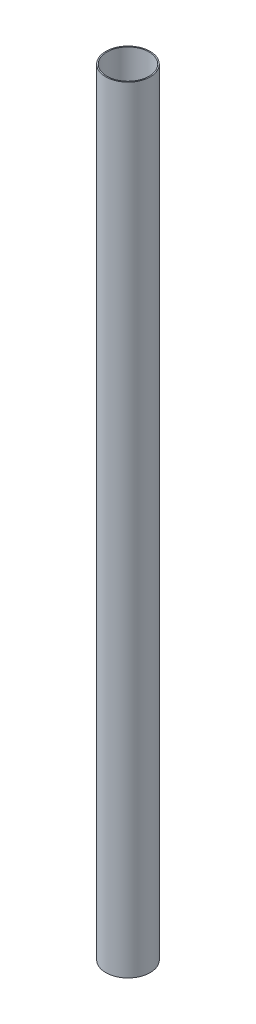
SolidWorks part; units mm, degrees
material "ПВХ 0.007 Смягченный"
ref_plane "Спереди" through (0, 0, 0) normal (0, 0, 1) x (1, 0, 0)
ref_plane "Сверху" through (0, 0, 0) normal (0, 1, 0) x (1, 0, 0)
ref_plane "Справа" through (0, 0, 0) normal (1, 0, 0) x (0, 0, -1)
sketch "Эскиз1" plane through (0, 0, 0) normal (0, 1, 0) x (1, 0, 0)
  circle A0 centre (0, 0) radius 20
  circle A1 centre (0, 0) radius 19
  dimension "ExDBody" = 40
  dimension "InDBody" = 38
extrude "Бобышка-Вытянуть1" add sketch "Эскиз1" along normal blind 700
